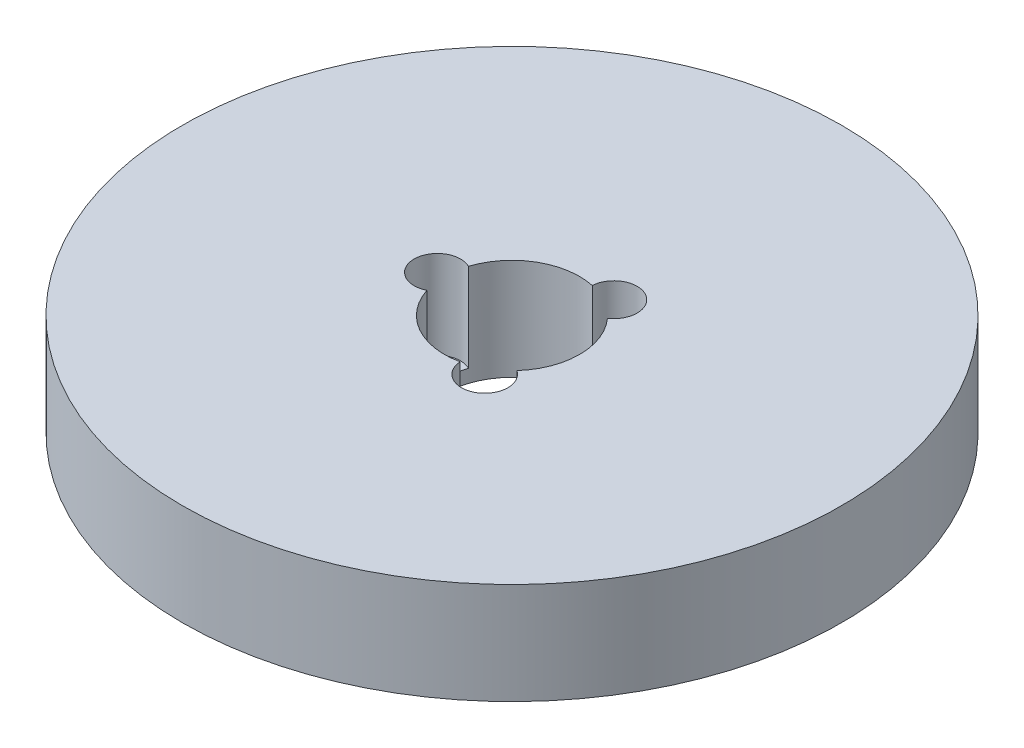
SolidWorks part; units mm, degrees
ref_plane "Front Plane" through (0, 0, 0) normal (0, 0, 1) x (1, 0, 0)
ref_plane "Top Plane" through (0, 0, 0) normal (0, 1, 0) x (1, 0, 0)
ref_plane "Right Plane" through (0, 0, 0) normal (1, 0, 0) x (0, 0, -1)
sketch "Sketch1" plane through (0, 0, 0) normal (0, 1, 0) x (1, 0, 0)
  circle A0 centre (0, 0) radius 97.5
  dimension "FLANGE_OD" = 195
extrude "Boss-Extrude1" add sketch "Sketch1" along normal blind 30
sketch "Sketch2" plane through (0, 0, 0) normal (0, 1, 0) x (1, 0, 0)
  circle A0 centre (0, 0) radius 20
  dimension "BORE_D" = 40
extrude "Cut-Extrude1" cut sketch "Sketch2" along normal through all
sketch "Sketch3" plane through (0, 30, 0) normal (0, 1, 0) x (1, 0, 0)
  circle A0 centre (0, 0) radius 22.0812 construction
  circle A1 centre (-22.0812, 0) radius 6.8679
  dimension "BOLT_D" = 13.7359
  dimension "BOLT_PCD" = 44.1623
extrude "Cut-Extrude2" cut sketch "Sketch3" against normal blind 26.1095
pattern_circular "CirPattern1" count 3 over 360 about axis through (0, 0, 0) along (0, 1, 0) of "Cut-Extrude2"
